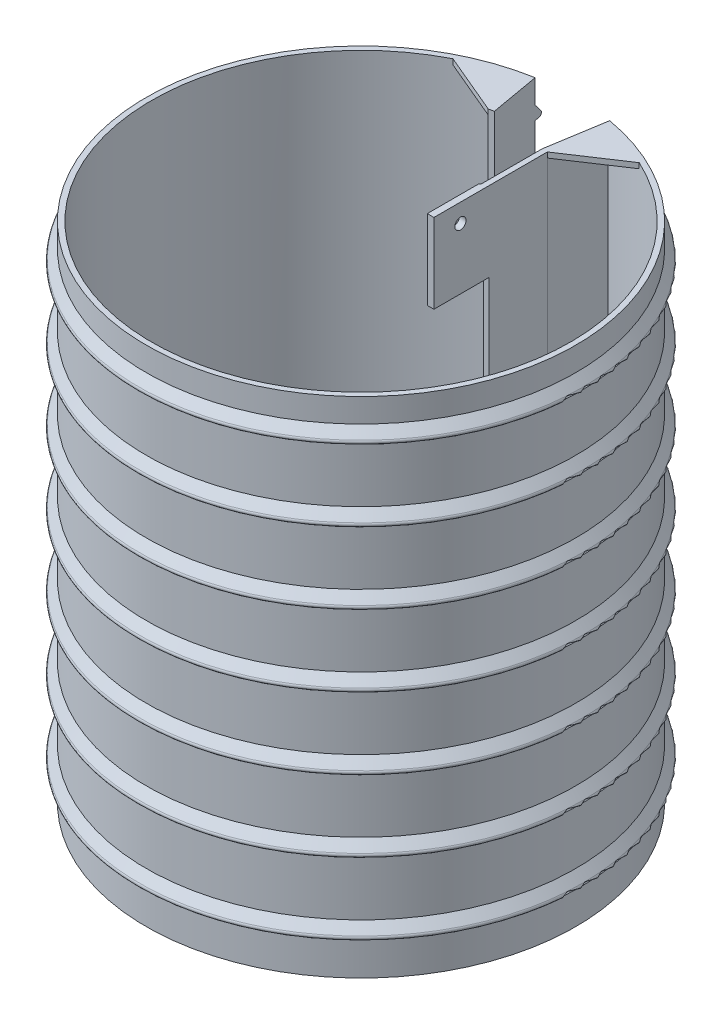
SolidWorks part; units mm, degrees
ref_plane "Plano frontal" through (0, 0, 0) normal (0, 0, 1) x (1, 0, 0)
ref_plane "Plano superior" through (0, 0, 0) normal (0, 1, 0) x (1, 0, 0)
ref_plane "Plano direito" through (0, 0, 0) normal (1, 0, 0) x (0, 0, -1)
sketch "Esboço1" plane through (0, 0, 0) normal (0, 1, 0) x (1, 0, 0)
  line L0 (0, 97.5906) -> (0, -93.5714) construction
  line L1 (-13.7182, 77.7998) -> (-14.0655, 79.7694)
  line L2 (13.7182, 77.7998) -> (14.0655, 79.7694)
  line L4 (12.5, 35.8) -> (12.5, 57.8)
  line L5 (10.5, 35.8) -> (10.5, 57.8)
  line L6 (10.5, 57.8) -> (13.7182, 77.7998)
  line L7 (12.5, 57.8) -> (15.6591, 77.4325)
  line L8 (12.5, 35.8) -> (10.5, 35.8)
  arc A0 (-14.0655, 79.7694) -> (14.0655, 79.7694) centre (0, 0) ccw
  arc A1 (-13.7182, 77.7998) -> (15.6591, 77.4325) centre (0, 0) ccw
  dimension "D1" = 10
  dimension "D3" = 81
  dimension "D4" = 79
  dimension "D2" = 10
  dimension "D5" = 2
  dimension "D6" = 1.9746
  dimension "D7" = 22
  dimension "D8" = 19.6325
extrude "Ressalto-extrusão1" add sketch "Esboço1" along normal blind 190
sketch "Esboço2" plane through (0, 0, 0) normal (0.9848, 0, -0.1736) x (-0.1736, 0, -0.9848)
  line L1 (81, 190) -> (81, 0) construction
  line L2 (81, 14) -> (82.9194, 14)
  line L4 (79, 0) -> (81, 0) construction
  line L5 (81, 19) -> (81, 14)
  line L6 (83.7002, 15.6247) -> (81, 19)
  arc A0 (82.9194, 14) -> (83.7002, 15.6247) centre (82.9194, 15) ccw
  point P5 (0, 0)
  point P7 (84, 17)
  point P10 (85, 14)
  point P11 (84, 16.9407)
  point P13 (85, 14)
  dimension "D4" = 1
  dimension "D1" = 4
  dimension "D2" = 14
  dimension "D3" = 5
ref_plane "Plano1" through (0, 13, 0) normal (0, 1, 0) x (1, 0, 0)
sketch "Esboço3" plane through (0, 13, 0) normal (0, 1, 0) x (1, 0, 0)
  arc A0 (-14.1523, 80.2618) -> (14.1523, 80.2618) centre (0, 0) ccw
  dimension "D1" = 163
sweep "Varredura1" add profiles "Esboço2" path "Esboço3"
pattern_linear "Padrão linear1" count 7 spacing 27 along (0, 1, 0) of "Varredura1"
sketch "Esboço4" plane through (0, 190, 0) normal (0, 1, 0) x (1, 0, 0)
  line L2 (10.5, 35.8) -> (10.5, 35)
  line L3 (10.5, 35) -> (10, 34.5)
  line L5 (10, 34.5) -> (10, 15)
  line L8 (12.5, 15) -> (12.5, 35.8)
  line L9 (10.5, 35.8) -> (12.5, 35.8)
  line L10 (10, 15) -> (12.5, 15)
extrude "Ressalto-extrusão2" add sketch "Esboço4" against normal blind 30
sketch "Esboço5" plane through (12.5, 0, 0) normal (1, 0, 0) x (0, 0, -1)
  line L2 (15, 190) -> (57.8, 190) construction
  line L6 (15, 160) -> (15, 190) construction
  circle A0 centre (25, 183) radius 2.1
  dimension "D1" = 4.2
  dimension "D2" = 10
  dimension "D3" = 7
extrude "Corte-extrusão1" cut sketch "Esboço5" against normal up to next contours A0
ref_plane "Plano2" through (-13.7182, 0, -77.7998) normal (0, -1, 0) x (-1, 0, 0)
sketch "Esboço6" plane through (0, 190, 0) normal (0, 1, 0) x (1, 0, 0)
  line L0 (-13.7182, 77.7998) -> (-10.7662, 61.0581)
  line L1 (-10.7662, 61.0581) -> (-12.7358, 60.7108)
  line L2 (-12.7358, 60.7108) -> (-16.2194, 77.3171)
  arc A0 (-13.7182, 77.7998) -> (15.6591, 77.4325) centre (0, 0) ccw construction
  arc A1 (-13.7182, 77.7998) -> (-16.2194, 77.3171) centre (0, 0) ccw
  dimension "D2" = 2
  dimension "D1" = 17
extrude "Ressalto-extrusão3" add sketch "Esboço6" against normal blind 165
sketch "Esboço7" plane through (0, 190, 0) normal (0, 1, 0) x (1, 0, 0)
  line L0 (-12.7358, 60.7108) -> (-35.7647, 70.4407)
  line L1 (12.5, 57.8) -> (33.3295, 71.625)
  line L11 (-16.2194, 77.3171) -> (-12.7358, 60.7108)
  line L12 (-12.7358, 60.7108) -> (-10.7662, 61.0581)
  line L13 (-10.7662, 61.0581) -> (-14.0655, 79.7694)
  line L14 (14.0655, 79.7694) -> (13.7182, 77.7998)
  line L15 (13.7182, 77.7998) -> (10.5, 57.8)
  line L16 (10.5, 57.8) -> (10.5, 35)
  line L17 (10.5, 35) -> (10, 34.5)
  line L18 (10, 34.5) -> (10, 15)
  line L19 (10, 15) -> (12.5, 15)
  line L20 (12.5, 15) -> (12.5, 57.8)
  line L21 (12.5, 57.8) -> (15.6591, 77.4325)
  line L22 (-16.2194, 77.3171) -> (-12.7358, 60.7108)
  line L25 (14.0655, 79.7694) -> (13.7182, 77.7998)
  line L28 (10.5, 35) -> (10, 34.5)
  line L32 (12.5, 57.8) -> (15.6591, 77.4325)
  arc A0 (33.3295, 71.625) -> (15.6591, 77.4325) centre (0, 0) ccw
  arc A2 (-16.2194, 77.3171) -> (15.6591, 77.4325) centre (0, 0) ccw
  arc A3 (-14.0655, 79.7694) -> (14.0655, 79.7694) centre (0, 0) ccw
  arc A4 (-16.2194, 77.3171) -> (-35.7647, 70.4407) centre (0, 0) ccw
  arc M16 (15.6591, 77.4325) -> (-16.2194, 77.3171) centre (0, 0) cw
  line M17 (-16.2194, 77.3171) -> (-12.7358, 60.7108)
  line M28 (12.5, 57.8) -> (15.6591, 77.4325)
  dimension "D2" = 25
  dimension "D3" = 25
  dimension "D1" = 0
extrude "Ressalto-extrusão4" add sketch "Esboço7" against normal blind 2 contours L1 M28 M16 | L0 M17 M16 region at (-21.8048, 190, -69.7281) region at (20.6425, 190, -69.1607)
